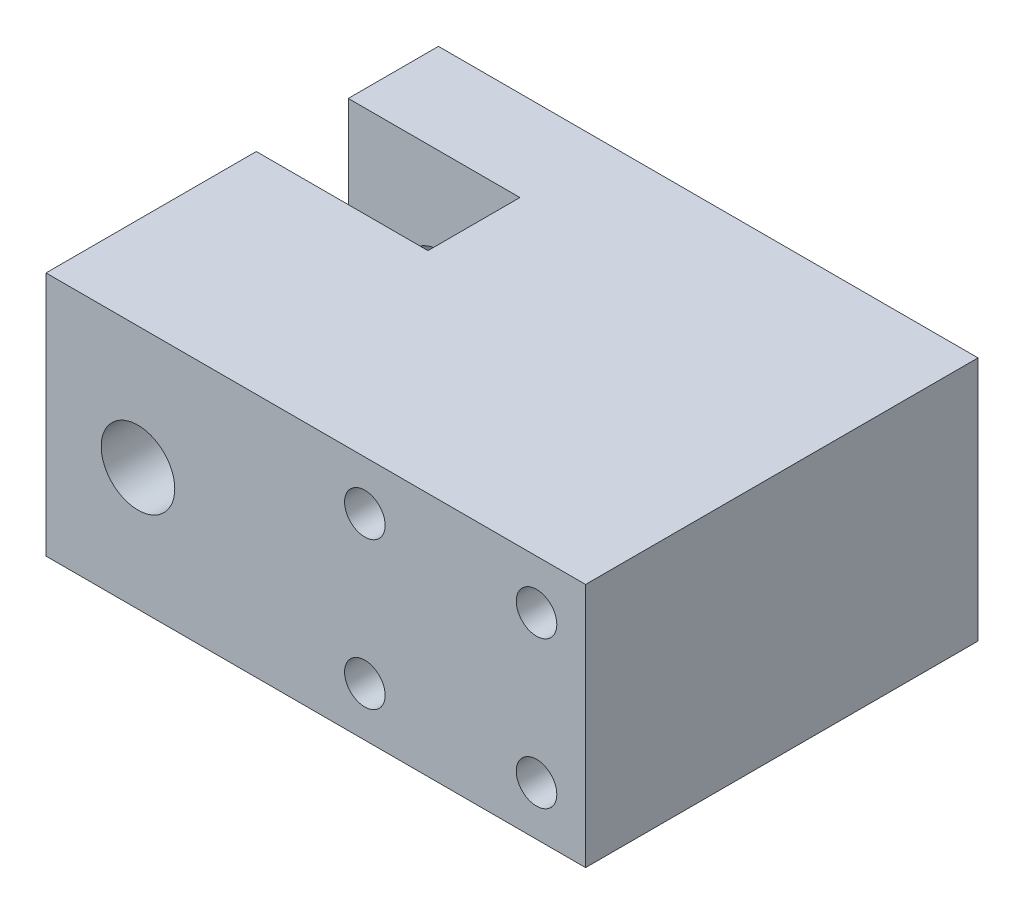
SolidWorks part; units mm, degrees
ref_plane "Front Plane" through (0, 0, 0) normal (0, 0, 1) x (1, 0, 0)
ref_plane "Top Plane" through (0, 0, 0) normal (0, 1, 0) x (1, 0, 0)
ref_plane "Right Plane" through (0, 0, 0) normal (1, 0, 0) x (0, 0, -1)
sketch "Sketch1" plane through (0, 0, 0) normal (0, 1, 0) x (1, 0, 0)
  line L1 (0, 0) -> (55.88, 0)
  line L2 (0, 0) -> (0, 40.64)
  line L3 (0, 40.64) -> (55.88, 40.64)
  line L4 (55.88, 0) -> (55.88, 40.64)
  dimension "D1" = 40.64
  dimension "D2" = 55.88
extrude "Boss-Extrude1" add sketch "Sketch1" along normal blind 25.4
sketch "Sketch3" plane through (0, 0, 0) normal (0, 0, 1) x (1, 0, 0)
  line L0 (0, 25.4) -> (0, 0) construction
  line L1 (0, 25.4) -> (55.88, 25.4) construction
  circle A0 centre (9.525, 12.7) radius 3.81
  dimension "D1" = 7.62
  dimension "D2" = 9.525
  dimension "D3" = 12.7
extrude "Cut-Extrude1" cut sketch "Sketch3" against normal through all
sketch "Sketch4" plane through (0, 25.4, 0) normal (0, 1, 0) x (1, 0, 0)
  line L0 (0, 40.64) -> (0, 0) construction
  line L1 (17.78, 31.3025) -> (0, 31.3025)
  line L2 (17.78, 31.3025) -> (17.78, 21.7775)
  line L3 (17.78, 21.7775) -> (0, 21.7775)
  line L4 (0, 31.3025) -> (0, 21.7775)
  line L5 (17.78, 31.3025) -> (0, 21.7775) construction
  line L6 (17.78, 21.7775) -> (0, 31.3025) construction
  line L7 (55.88, 40.64) -> (0, 40.64) construction
  point P0 (8.89, 26.54)
  dimension "D1" = 14.1
  dimension "D2" = 9.525
  dimension "D3" = 17.78
extrude "Cut-Extrude2" cut sketch "Sketch4" against normal through all
hole_wizard "M5x0.8 Tapped Hole1" positions "Sketch7" profile "Sketch6" tap size "M5x0.8" standard "ANSI Metric"
sketch "Sketch7" plane through (0, 0, 0) normal (0, 0, 1) x (1, 0, 0)
  line L0 (0, 0) -> (55.88, 0) construction
  line L1 (55.88, 25.4) -> (55.88, 0) construction
  point P0 (50.8, 5.08)
  point P11 (33.02, 5.08)
  point P12 (33.02, 20.32)
  point P13 (50.8, 20.32)
  dimension "D1" = 5.08
  dimension "D2" = 5.08
  dimension "D3" = 2
  dimension "D4" = 2
sketch "Sketch6" plane through (50.8, 5.08, 0) normal (1, 0, 0) x (0, -1, 0)
  line L0 (0, 0) -> (0, 26.6618)
  line L1 (0, 26.6618) -> (2.1, 25.4)
  line L2 (2.1, 25.4) -> (2.1, 0)
  line L5 (2.1, 0) -> (0, 0)
  line L10 (0, 26.6618) -> (-2.1, 25.4) construction
  line L11 (0, -6.35) -> (0, 107.95) construction
  dimension "Tap Drill Dia." = 4.2
  dimension "Tap Drill Depth" = 25.4
  dimension "Drill Angle" = 118
cosmetic thread "Hole Thread1" parameters "D1"=20.32, "D2"=5
cosmetic thread "Hole Thread2" parameters "D1"=20.32, "D2"=5
cosmetic thread "Hole Thread3" parameters "D1"=20.32, "D2"=5
cosmetic thread "Hole Thread4" parameters "D1"=20.32, "D2"=5
